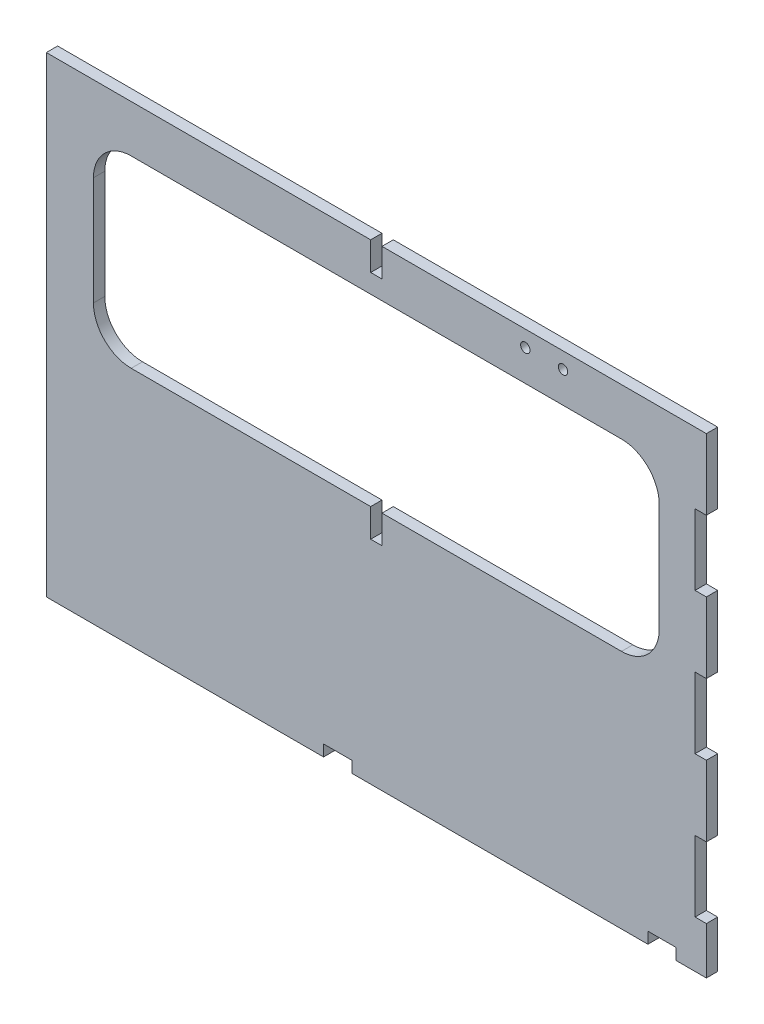
SolidWorks part; units mm, degrees
ref_plane "Front" through (0, 0, 0) normal (0, 0, 1) x (1, 0, 0)
ref_plane "Top" through (0, 0, 0) normal (0, 1, 0) x (1, 0, 0)
ref_plane "Right" through (0, 0, 0) normal (1, 0, 0) x (0, 0, -1)
sketch "Sketch1" plane through (0, 0, 0) normal (0, 0, 1) x (1, 0, 0)
  line L1 (0, 0) -> (-200, 0)
  line L2 (0, 0) -> (0, 150)
  line L4 (-200, 0) -> (-200, 150)
  line L5 (-100, 90) -> (-100, 0) construction
  line L6 (-175, 110) -> (-175, 125)
  line L7 (-25, 110) -> (-25, 125)
  line L9 (-175, 125) -> (-25, 125)
  line L11 (-200, 150) -> (0, 150)
  arc A0 (-153.0972, 57.0313) -> (-46.9028, 57.0312) centre (-100, 90) ccw
  arc A1 (-175, 110) -> (-153.0972, 57.0313) centre (-100, 110) ccw
  arc A2 (-46.9028, 57.0312) -> (-25, 110) centre (-100, 110) ccw
  dimension "D3" = 62.5
  dimension "D4" = 75
  dimension "D1" = 200
  dimension "D2" = 25
  dimension "D5" = 20
  dimension "D6" = 90
  dimension "D7" = 150
extrude "Boss-Extrude1" add sketch "Sketch1" along normal blind 6
sketch "Sketch3" plane through (0, 0, 6) normal (0, 0, 1) x (1, 0, 0)
  line L0 (-200, 150) -> (-200, 0) construction
  line L1 (-100, 27.5) -> (-200, 27.5)
  line L2 (-100, 27.5) -> (-100, 125)
  line L3 (-100, 125) -> (-200, 125)
  line L4 (-200, 27.5) -> (-200, 125)
  line L7 (-25, 125) -> (-175, 125) construction
  arc A0 (-153.0972, 57.0313) -> (-46.9028, 57.0312) centre (-100, 90) ccw construction
extrude "Cut-Extrude1" cut sketch "Sketch3" against normal blind 6
sketch "Sketch4" plane through (0, 0, 6) normal (0, 0, 1) x (1, 0, 0)
  line L0 (-250, 110) -> (-100, 110) construction
  line L1 (-100, 90) -> (-250, 90) construction
  line L2 (-250, 90) -> (-250, 110) construction
  line L3 (-25, 125) -> (0, 125) construction
  line L4 (-200, 27.5) -> (-250, 27.5)
  line L5 (-200, 27.5) -> (-200, 0)
  line L6 (-200, 0) -> (-350, 0)
  line L9 (-350, 0) -> (-350, 150)
  line L11 (-325, 110) -> (-325, 125)
  line L12 (-200, 125) -> (-325, 125)
  line L13 (-200, 125) -> (-200, 150)
  line L14 (-200, 150) -> (-350, 150)
  line L16 (0, 0) -> (0, 150) construction
  line L17 (-325, 125) -> (-350, 125) construction
  line L18 (-200, 0) -> (0, 0) construction
  arc A0 (-325, 110) -> (-303.0972, 57.0312) centre (-250, 110) ccw
  circle A1 centre (-100, 90) radius 62.5 construction
  circle A2 centre (-100, 110) radius 75 construction
  arc A3 (-46.9028, 57.0312) -> (-25, 110) centre (-100, 110) ccw construction
  arc A4 (-100, 27.5) -> (-46.9028, 57.0312) centre (-100, 90) ccw construction
  arc A5 (-303.0972, 57.0312) -> (-250, 27.5) centre (-250, 90) ccw
  dimension "D1" = 150
  dimension "D2" = 125
  dimension "D4" = 125
  dimension "D3" = 150
extrude "Boss-Extrude3" add sketch "Sketch4" against normal blind 6
sketch "Sketch5" plane through (0, 0, 6) normal (0, 0, 1) x (1, 0, 0)
  line L1 (-178, 150) -> (-172, 150)
  line L2 (-178, 150) -> (-178, 135)
  line L3 (-178, 135) -> (-172, 135)
  line L4 (-172, 150) -> (-172, 135)
  line L5 (-250, 27.5) -> (-100, 27.5) construction
  line L6 (-178, 27.5) -> (-172, 27.5)
  line L7 (-178, 27.5) -> (-178, 12.5)
  line L8 (-178, 12.5) -> (-172, 12.5)
  line L9 (-172, 27.5) -> (-172, 12.5)
  line L10 (0, 150) -> (-350, 150) construction
  point P12 (-175, 150)
  point P14 (-175, 150)
  dimension "D1" = 6
  dimension "D2" = 15
extrude "Cut-Extrude2" cut sketch "Sketch5" against normal blind 6
sketch "Sketch6" plane through (0, 0, 6) normal (0, 0, 1) x (1, 0, 0)
  line L0 (0, 0) -> (0, 150) construction
  line L1 (0, 112.5) -> (-6, 112.5)
  line L2 (0, 112.5) -> (0, 75)
  line L3 (0, 75) -> (-6, 75)
  line L4 (-6, 112.5) -> (-6, 75)
  line L5 (0, 150) -> (-172, 150) construction
  dimension "D1" = 37.5
  dimension "6" = 6
  dimension "D2" = 37.5
extrude "Cut-Extrude3" cut sketch "Sketch6" against normal blind 6
sketch "Sketch8" plane through (0, 0, 6) normal (0, 0, 1) x (1, 0, 0)
  line L1 (-350, 0) -> (0, 0)
  line L2 (-350, 0) -> (-350, -100)
  line L3 (-350, -100) -> (0, -100)
  line L4 (0, 0) -> (0, -100)
  dimension "D1" = 100
extrude "Boss-Extrude4" add sketch "Sketch8" against normal up to surface (6 mm away) up to face at (-117.6667, 103.75, 0)
pattern_linear "LPattern1" count 3 spacing 75 along (0, -1, 0) of "Cut-Extrude3"
sketch "Sketch7" plane through (0, 0, 6) normal (0, 0, 1) x (1, 0, 0)
  line L1 (-16, -100) -> (-31, -100)
  line L2 (-16, -100) -> (-16, -94)
  line L3 (-16, -94) -> (-31, -94)
  line L4 (-31, -100) -> (-31, -94)
  line L5 (-6, -37.5) -> (-6, -75) construction
  line L6 (-350, -100) -> (0, -100) construction
  line L7 (-178, 27.5) -> (-178, 12.5) construction
  line L8 (-188, -100) -> (-203, -100)
  line L9 (-188, -100) -> (-188, -94)
  line L10 (-188, -94) -> (-203, -94)
  line L11 (-203, -100) -> (-203, -94)
  dimension "D1" = 15
  dimension "D2" = 10
  dimension "D3" = 6
  dimension "D4" = 10
extrude "s" cut sketch "Sketch7" against normal through all
sketch "Sketch9" plane through (0, 0, 6) normal (0, 0, 1) x (1, 0, 0)
  line L0 (-25, 110) -> (-25, 125) construction
  line L1 (-325, 125) -> (-25, 125)
  line L2 (-325, 125) -> (-325, 27.5)
  line L3 (-325, 27.5) -> (-25, 27.5)
  line L4 (-25, 125) -> (-25, 27.5)
  line L5 (-250, 27.5) -> (-178, 27.5) construction
extrude "Cut-Extrude4" cut sketch "Sketch9" against normal through all
fillet "Fillet1" radius 20 4 edges at (-25, 27.5, 3) (-25, 125, 3) (-325, 27.5, 3) (-325, 125, 3)
sketch "Sketch10" plane through (0, 0, 6) normal (0, 0, 1) x (1, 0, 0)
  line L0 (0, 112.5) -> (0, 150) construction
  line L1 (0, 150) -> (-172, 150) construction
  circle A0 centre (-96, 141.5) radius 2.5
  circle A1 centre (-76, 141.5) radius 2.5
  point P8 (0, 0)
  dimension "D3" = 5
  dimension "D1" = 76
  dimension "D2" = 20
  dimension "D4" = 8.5
extrude "Cut-Extrude5" cut sketch "Sketch10" against normal through all
